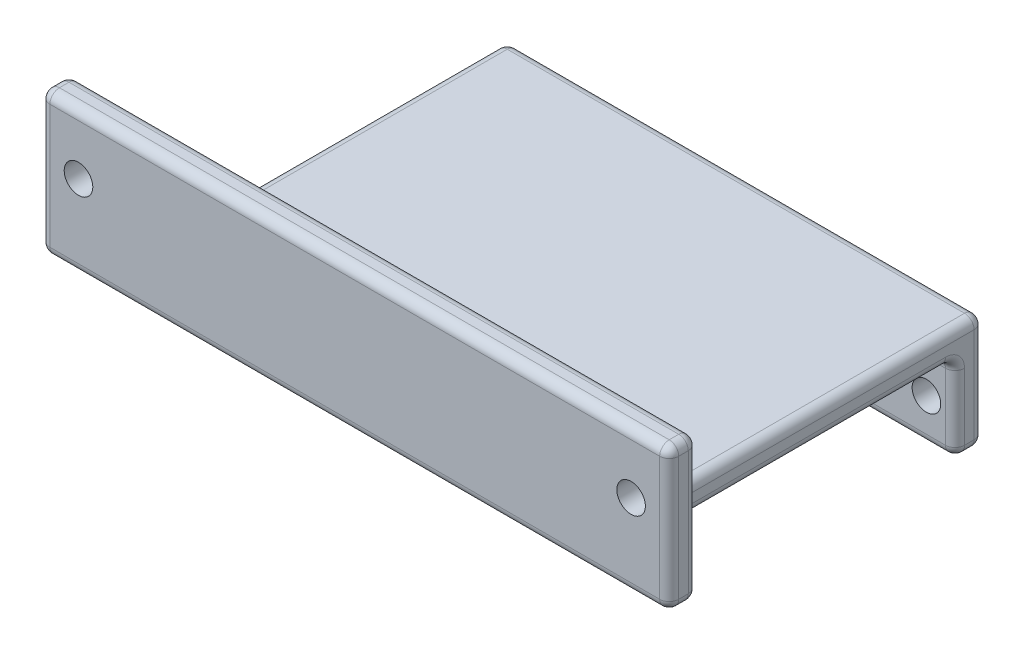
SolidWorks part; units mm, degrees
ref_plane "Piano frontale" through (0, 0, 0) normal (0, 0, 1) x (1, 0, 0)
ref_plane "Piano superiore" through (0, 0, 0) normal (0, 1, 0) x (1, 0, 0)
ref_plane "Piano destro" through (0, 0, 0) normal (1, 0, 0) x (0, 0, -1)
sketch "Schizzo1" plane through (0, 0, 0) normal (0, 0, 1) x (1, 0, 0)
  line L1 (25, -6) -> (-25, -6)
  line L2 (25, -6) -> (25, 6)
  line L3 (25, 6) -> (-25, 6)
  line L4 (-25, -6) -> (-25, 6)
  line L5 (25, -6) -> (-25, 6) construction
  line L6 (25, 6) -> (-25, -6) construction
  point P0 (0, 0)
  dimension "D1" = 12
  dimension "D2" = 50
extrude "Estrusione-Estrusione1" add sketch "Schizzo1" along normal blind 3 contours L1 L4 L3 L2
sketch "Schizzo2" plane through (0, 0, 3) normal (0, 0, 1) x (1, 0, 0)
  line L0 (25, -6) -> (25, 6) construction
  line L1 (-25, 6) -> (25, 6)
  line L2 (-25, 6) -> (-25, 3)
  line L3 (-25, 3) -> (25, 3)
  line L4 (25, 6) -> (25, 3)
  dimension "D1" = 3
extrude "Estrusione-Estrusione2" add sketch "Schizzo2" along normal blind 35
sketch "Schizzo3" plane through (0, 0, 38) normal (0, 0, 1) x (1, 0, 0)
  line L0 (33, 18) -> (33, 3)
  line L6 (33, 3) -> (-33, 3)
  line L22 (-33, 3) -> (-33, 18)
  line L27 (33, 18) -> (-33, 18)
extrude "Estrusione-Estrusione3" add sketch "Schizzo3" along normal blind 3
sketch "Schizzo5" plane through (0, 0, 41) normal (0, 0, 1) x (1, 0, 0)
  line L2 (33, 6) -> (-33, 6) construction
  line L3 (33, 3) -> (33, 18) construction
  line L4 (-33, 18) -> (-33, 3) construction
  line L6 (-33, 3) -> (33, 3) construction
  circle A8 centre (-29, 11.72) radius 1.5
  circle A9 centre (29, 11.72) radius 1.5
  dimension "D1" = 3
extrude "Taglio-Estrusione1" cut sketch "Schizzo5" against normal blind 6
sketch "Schizzo6" plane through (0, 0, 0) normal (0, 0, -1) x (-1, 0, 0)
  line L0 (-25, 3) -> (25, 3) construction
  line L3 (-25, 3) -> (25, -6) construction
  line L5 (25, -6) -> (25, 6) construction
  line L6 (-25, -6) -> (25, -6) construction
  line L7 (-25, -6) -> (25, 3) construction
  line L8 (0, -1.5) -> (-25, -1.5) construction
  line L9 (-25, -6) -> (-25, 6) construction
  line L10 (0, -1.5) -> (0, -6) construction
  circle A2 centre (-22, -1.5) radius 1.5
  circle A3 centre (22, -1.5) radius 1.5
  dimension "D1" = 3
  dimension "D2" = 22
extrude "Taglio-Estrusione2" cut sketch "Schizzo6" against normal blind 6
fillet "Raccordo1" radius 1 30 edges at (-25, 4.5, 38) (25, 4.5, 38) (29, 3, 38) (-29, 3, 38) (-25, 6, 19) (-25, 3, 20.5) (-25, -6, 1.5) (-25, -1.5, 3) (25, 3, 20.5) (25, 6, 19) (25, -6, 1.5) (0, -6, 3) (25, -1.5, 3) (25, 0, 0) (0, -6, 0) (-25, 0, 0) (0, 6, 0) (0, 3, 3) (0, 6, 38) (33, 10.5, 41) (33, 3, 39.5) (33, 10.5, 38) (33, 18, 39.5) (0, 18, 38) (0, 18, 41) (-33, 18, 39.5) (0, 3, 41) (-33, 3, 39.5) (-33, 10.5, 38) (-33, 10.5, 41)
